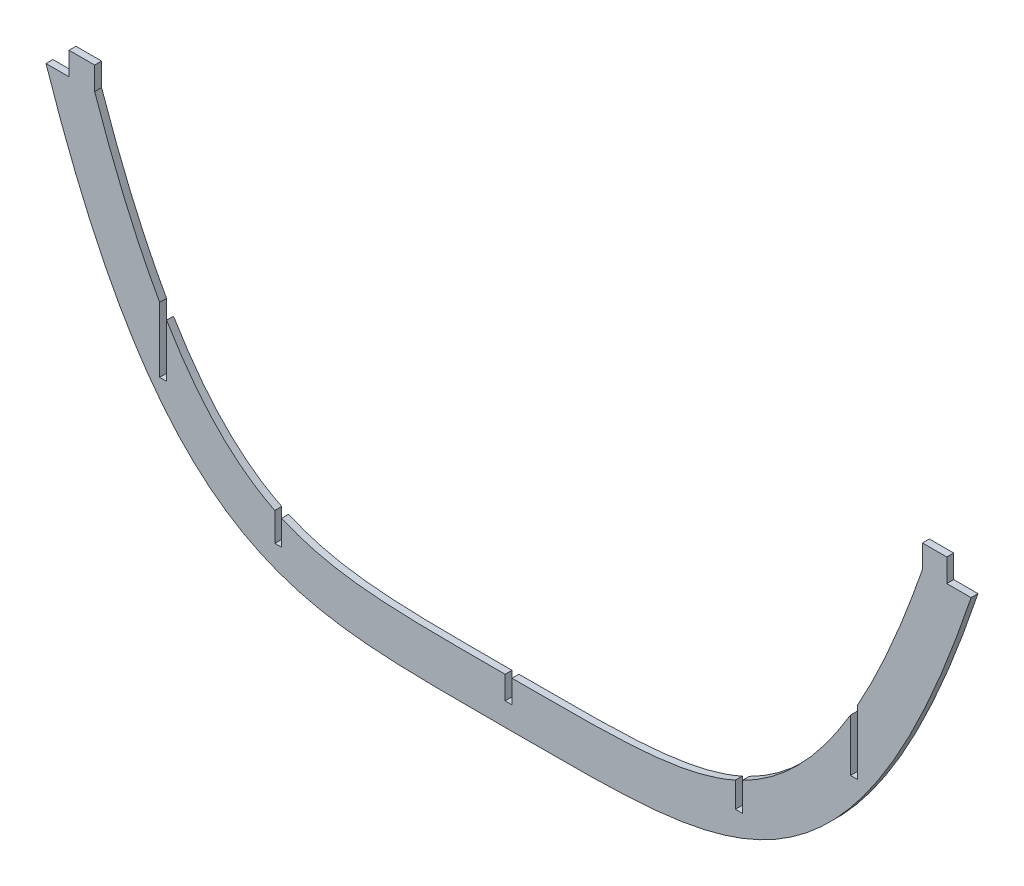
SolidWorks part; units mm, degrees
ref_plane "Front Plane" through (0, 0, 0) normal (0, 0, 1) x (1, 0, 0)
ref_plane "Top Plane" through (0, 0, 0) normal (0, 1, 0) x (1, 0, 0)
ref_plane "Right Plane" through (0, 0, 0) normal (1, 0, 0) x (0, 0, -1)
sketch "Sketch1" plane through (0, 0, 0) normal (0, 0, 1) x (1, 0, 0)
  line L5 (-190.8571, 160) -> (-179.7305, 160)
  line L6 (-179.7305, 160) -> (-179.7305, 150)
  line L8 (190.2938, 160) -> (179.7305, 160)
  line L9 (179.7305, 160) -> (179.7305, 150)
  line L10 (-200.8571, 150) -> (-190.8571, 150)
  line L11 (-190.8571, 150) -> (-190.8571, 160)
  line L12 (190.2938, 160) -> (190.2938, 150)
  line L13 (190.2938, 150) -> (200.8571, 150)
  spline S0 degree 4 poles (-216.8089, 203.6342) (-108.4044, -203.6342) (0, 203.6342) (108.4044, -203.6342) (216.8089, 203.6342) knots 0 0 0 0 0 1 1 1 1 1 construction
  spline S1 degree 4 poles (-200.8571, 150) (-100.4286, -150) (0, 150) (100.4286, -150) (200.8571, 150) knots 0.036788 0.036788 0.036788 0.036788 0.036788 0.963212 0.963212 0.963212 0.963212 0.963212
  spline S2 degree 1 poles (-181.8916, 156.3489) (181.8916, 156.3489) knots 0 0 1 1 construction
  spline S3 degree 3 poles (-181.8916, 156.3489) (-181.3891, 154.848) (-180.3653, 151.8253) (-178.3412, 145.9898) (-175.81, 138.9489) (-172.7858, 130.9351) (-168.7678, 120.7983) (-163.7768, 109.1306) (-157.8474, 96.6329) (-151.9892, 85.5414) (-144.2887, 72.4973) (-134.9007, 59.2193) (-124.0868, 47.3263) (-113.706, 38.6442) (-103.5943, 32.3808) (-93.4771, 27.8904) (-83.0914, 24.7263) (-68.685, 21.8783) (-49.5164, 20.3042) (-25.1066, 19.9753) (0, 20.0124) (25.1066, 19.9753) (49.5164, 20.3042) (68.685, 21.8783) (83.0914, 24.7263) (93.4771, 27.8904) (103.5943, 32.3808) (113.706, 38.6442) (124.0868, 47.3263) (134.9007, 59.2193) (144.2887, 72.4973) (151.9892, 85.5414) (157.8474, 96.6329) (163.7768, 109.1306) (168.7678, 120.7983) (172.7858, 130.9351) (175.81, 138.9489) (178.3412, 145.9898) (180.3653, 151.8253) (181.3891, 154.848) (181.8916, 156.3489) knots 0.036788 0.036788 0.036788 0.036788 0.040406 0.044025 0.051263 0.058501 0.065738 0.080214 0.094689 0.109165 0.12364 0.152591 0.181541 0.210492 0.239443 0.268394 0.297345 0.326295 0.384197 0.442098 0.5 0.557902 0.615803 0.673705 0.702655 0.731606 0.760557 0.789508 0.818459 0.847409 0.87636 0.890835 0.905311 0.919786 0.934262 0.941499 0.948737 0.955975 0.959594 0.963212 0.963212 0.963212 0.963212 only from (-179.7305, 150) to (179.7305, 150)
  dimension "D1" = 20
extrude "Boss-Extrude1" add sketch "Sketch1" along normal blind 3 contours S1 L13 L12 L8 L9 S3 L6 L5 L11 L10
sketch "Sketch2" plane through (0, 0, 0) normal (0, 0, 1) x (1, 0, 0)
  line L8 (1.5, 10) -> (-1.5, 10)
  line L12 (-1.5, 10) -> (-1.5, 21.3682)
  line L13 (-1.5, 21.3682) -> (1.5, 21.3682)
  line L14 (1.5, 10) -> (1.5, 21.3682)
extrude "Cut-Extrude2" cut sketch "Sketch2" along normal blind 22
sketch "Sketch4" plane through (0, 0, 0) normal (0, 0, 1) x (1, 0, 0)
  line L5 (101.5, 19.216) -> (98.5, 19.216)
  line L6 (101.5, 19.216) -> (101.5, 32.1285)
  line L7 (101.5, 32.1285) -> (98.5, 32.1285)
  line L8 (98.5, 19.216) -> (98.5, 32.1285)
extrude "Cut-Extrude3" cut sketch "Sketch4" along normal blind 45
sketch "Sketch5" plane through (0, 0, 0) normal (0, 0, 1) x (1, 0, 0)
  line L5 (-98.5, 19.216) -> (-101.5, 19.216)
  line L6 (-98.5, 19.216) -> (-98.5, 36.9515)
  line L7 (-98.5, 36.9515) -> (-101.5, 36.9515)
  line L8 (-101.5, 19.216) -> (-101.5, 36.9515)
extrude "Cut-Extrude4" cut sketch "Sketch5" along normal blind 38
sketch "Sketch6" plane through (0, 0, 0) normal (0, 0, 1) x (1, 0, 0)
  line L6 (-148.5, 56.656) -> (-151.5, 56.656)
  line L7 (-148.5, 56.656) -> (-148.5, 87.4942)
  line L8 (-148.5, 87.4942) -> (-151.5, 87.4942)
  line L9 (-151.5, 56.656) -> (-151.5, 87.4942)
extrude "Cut-Extrude5" cut sketch "Sketch6" along normal blind 99
sketch "Sketch7" plane through (0, 0, 0) normal (0, 0, 1) x (1, 0, 0)
  line L2 (148.5, 59.9497) -> (148.5, 86.6745)
  line L3 (148.5, 59.9497) -> (148.5, 56.9497)
  line L4 (148.5, 56.9497) -> (151.5, 56.9497)
  line L5 (151.5, 56.9497) -> (151.5, 59.9497)
  line L7 (151.5, 59.9497) -> (151.5, 86.6745)
  line L8 (151.5, 86.6745) -> (148.5, 86.6745)
extrude "Cut-Extrude6" cut sketch "Sketch7" along normal blind 239
